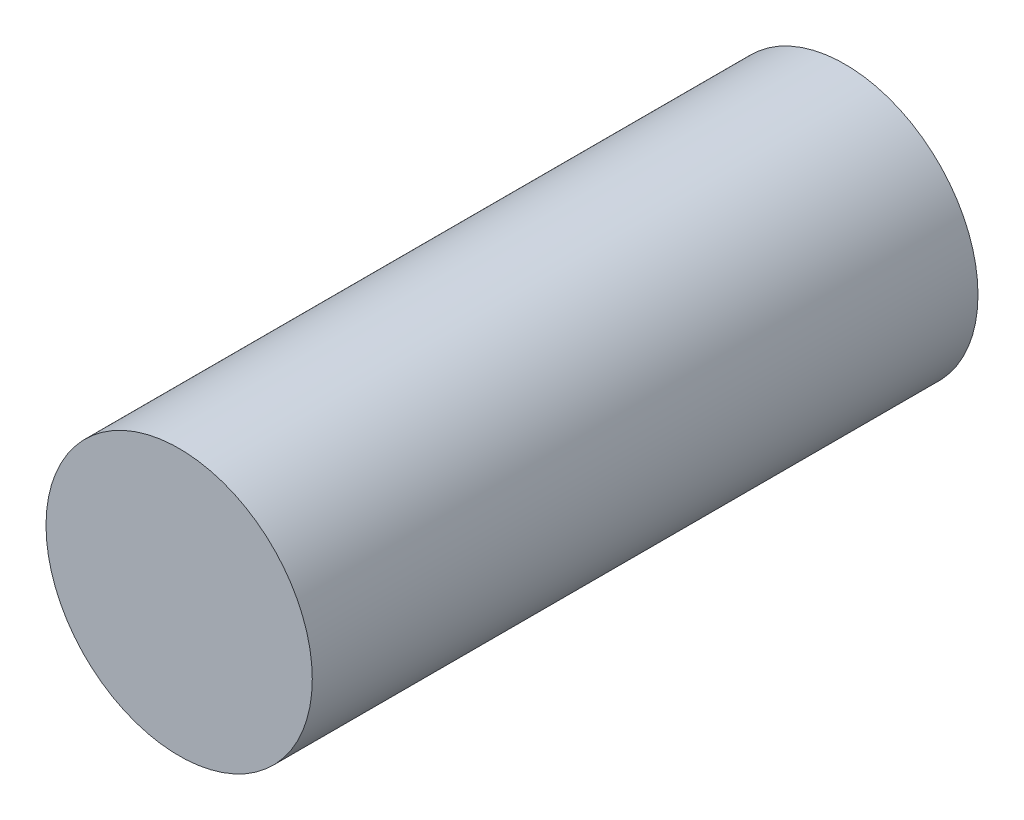
SolidWorks part; units mm, degrees
material "普通碳钢"
ref_plane "前视基准面" through (0, 0, 0) normal (0, 0, 1) x (1, 0, 0)
ref_plane "上视基准面" through (0, 0, 0) normal (0, 1, 0) x (1, 0, 0)
ref_plane "右视基准面" through (0, 0, 0) normal (1, 0, 0) x (0, 0, -1)
sketch "草图1" plane through (0, 0, 0) normal (0, 0, 1) x (1, 0, 0)
  circle A0 centre (0, 0) radius 30
  dimension "D1" = 60
extrude "凸台-拉伸1" add sketch "草图1" along normal blind 150
ref_axis "基准轴1" through (0, 0, 150) along (0, 0, -1)
